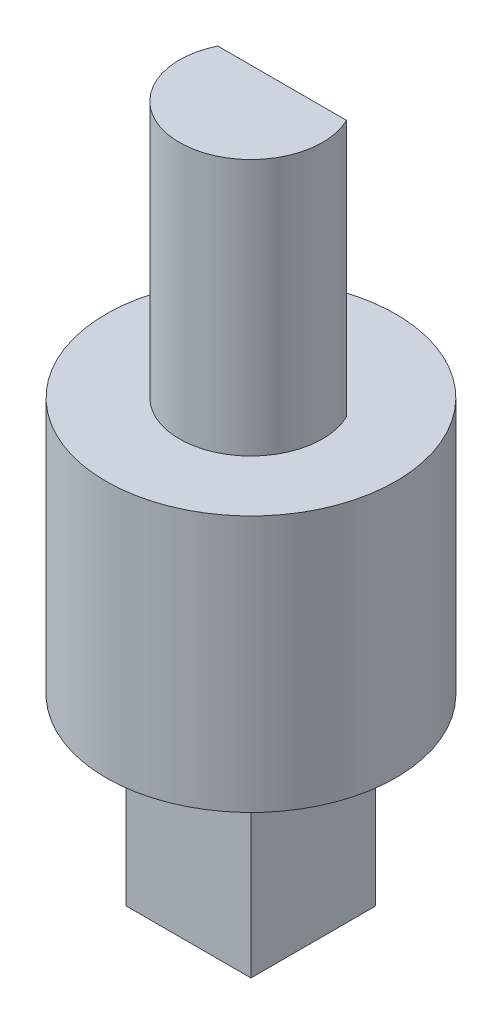
SolidWorks part; units mm, degrees
ref_plane "Front Plane" through (0, 0, 0) normal (0, 0, 1) x (1, 0, 0)
ref_plane "Top Plane" through (0, 0, 0) normal (0, 1, 0) x (1, 0, 0)
ref_plane "Right Plane" through (0, 0, 0) normal (1, 0, 0) x (0, 0, -1)
sketch "Sketch1" plane through (0, 0, 0) normal (0, 1, 0) x (1, 0, 0)
  line L1 (-1.7, -1.7) -> (1.7, -1.7)
  line L2 (-1.7, -1.7) -> (-1.7, 1.7)
  line L3 (-1.7, 1.7) -> (1.7, 1.7)
  line L4 (1.7, -1.7) -> (1.7, 1.7)
  line L5 (-1.7, -1.7) -> (1.7, 1.7) construction
  line L6 (-1.7, 1.7) -> (1.7, -1.7) construction
  point P0 (0, 0)
  dimension "D1" = 3.4
  dimension "D2" = 3.4
extrude "Boss-Extrude1" add sketch "Sketch1" along normal blind 5
sketch "Sketch2" plane through (0, 5, 0) normal (0, 1, 0) x (1, 0, 0)
  circle A0 centre (0, 0) radius 3.95
  dimension "D1" = 7.9
extrude "Boss-Extrude2" add sketch "Sketch2" along normal blind 7
sketch "Sketch3" plane through (0, 12, 0) normal (0, 1, 0) x (1, 0, 0)
  circle A0 centre (0, 0) radius 1.95
  dimension "D1" = 3.9
extrude "Boss-Extrude3" add sketch "Sketch3" along normal blind 7
sketch "Sketch4" plane through (0, 19, 0) normal (0, 1, 0) x (1, 0, 0)
  line L0 (0, -1.95) -> (0, 0.85) construction
  line L1 (0, 0.85) -> (1.755, 0.85) construction
  line L2 (0, 0.85) -> (-1.755, 0.85) construction
  line L3 (-1.755, 0.85) -> (1.755, 0.85)
  circle A0 centre (0, 0) radius 1.95 construction
  circle A1 centre (0, 0) radius 1.95 construction
  arc A2 (-1.755, 0.85) -> (1.755, 0.85) centre (0, 0) cw
  dimension "D1" = 2.8
extrude "Cut-Extrude1" cut sketch "Sketch4" against normal blind 7
